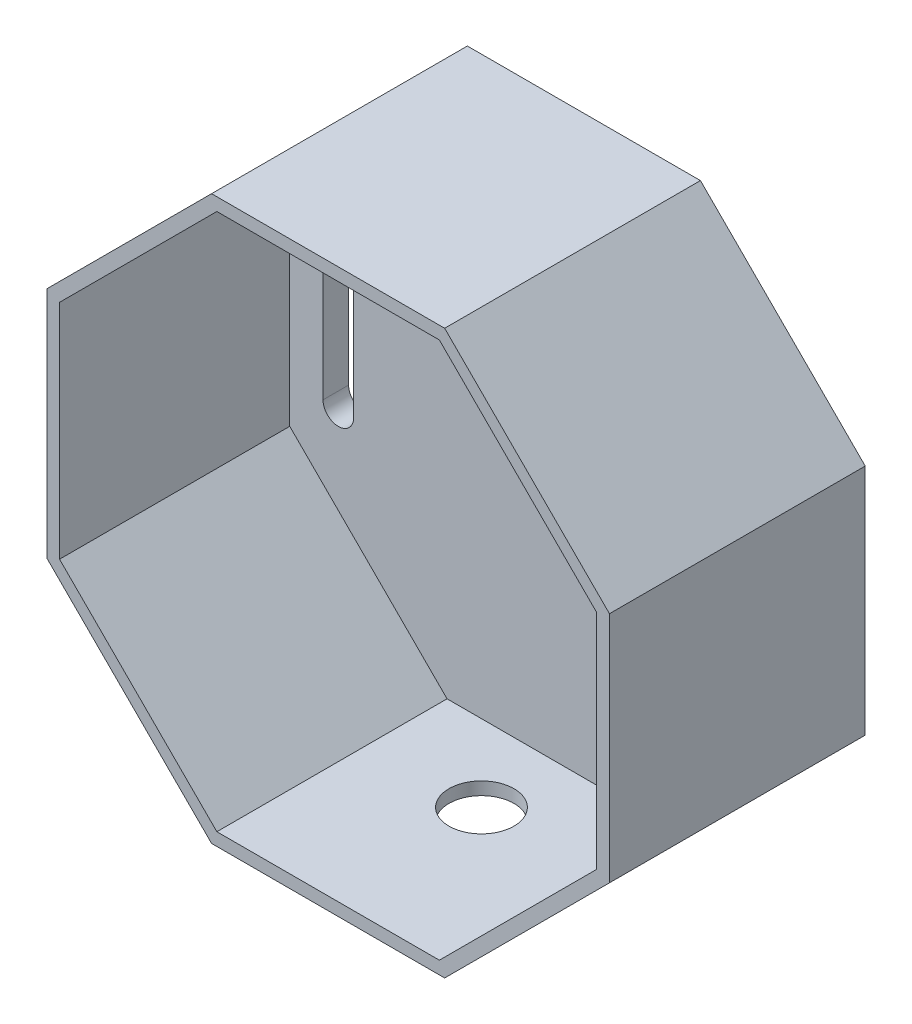
SolidWorks part; units mm, degrees
material "ABS PC"
ref_plane "Front Plane" through (0, 0, 0) normal (0, 0, 1) x (1, 0, 0)
ref_plane "Top Plane" through (0, 0, 0) normal (0, 1, 0) x (1, 0, 0)
ref_plane "Right Plane" through (0, 0, 0) normal (1, 0, 0) x (0, 0, -1)
sketch "Sketch8" plane through (0, 0, 0) normal (0, 0, 1) x (1, 0, 0)
  line L1 (55, 22.7817) -> (22.7817, 55)
  line L2 (22.7817, 55) -> (-22.7817, 55)
  line L3 (-22.7817, 55) -> (-55, 22.7817)
  line L4 (-55, 22.7817) -> (-55, -22.7817)
  line L5 (-55, -22.7817) -> (-22.7817, -55)
  line L6 (-22.7817, -55) -> (22.7817, -55)
  line L7 (22.7817, -55) -> (55, -22.7817)
  line L8 (55, -22.7817) -> (55, 22.7817)
  circle A0 centre (0, 0) radius 55 construction
extrude "Boss-Extrude3" add sketch "Sketch8" along normal blind 50
sketch "Sketch9" plane through (0, 0, 50) normal (0, 0, 1) x (1, 0, 0)
  line L1 (52.5, 21.7462) -> (21.7462, 52.5)
  line L2 (21.7462, 52.5) -> (-21.7462, 52.5)
  line L3 (-21.7462, 52.5) -> (-52.5, 21.7462)
  line L4 (-52.5, 21.7462) -> (-52.5, -21.7462)
  line L5 (-52.5, -21.7462) -> (-21.7462, -52.5)
  line L6 (-21.7462, -52.5) -> (21.7462, -52.5)
  line L7 (21.7462, -52.5) -> (52.5, -21.7462)
  line L8 (52.5, -21.7462) -> (52.5, 21.7462)
  circle A0 centre (0, 0) radius 52.5 construction
extrude "Cut-Extrude3" cut sketch "Sketch9" against normal blind 45
hole_wizard "Hole1" positions "Sketch10" profile "Sketch12" legacy end condition through all
sketch "Sketch10" plane through (0, -52.5, 0) normal (0, 1, 0) x (1, 0, 0)
  point P0 (0, -20.0175)
sketch "Sketch12" plane through (0, -52.5, 20.0175) normal (1, 0, 0) x (0, 0, 1)
  line L0 (0, 0) -> (0, 2.5)
  line L1 (0, 2.5) -> (6.35, 2.5)
  line L2 (6.35, 2.5) -> (6.35, 0)
  line L3 (6.35, 0) -> (0, 0)
  line L4 (0, 110) -> (0, -10) construction
  dimension "Diameter" = 12.7
  dimension "Depth" = 2.5
sketch "Sketch15" plane through (0, 0, 0) normal (0, 0, -1) x (-1, 0, 0)
  line L0 (-43, 13.2597) -> (-43, -13.2907) construction
  line L1 (-40, 13.2597) -> (-40, -13.2907)
  line L2 (-46, 13.2597) -> (-46, -13.2907)
  line L3 (-52.5, -21.7462) -> (-52.5, 21.7462) construction
  arc A0 (-40, 13.2597) -> (-46, 13.2597) centre (-43, 13.2597) ccw
  arc A1 (-46, -13.2907) -> (-40, -13.2907) centre (-43, -13.2907) ccw
  point P2 (-43, -0.0155)
  point P7 (-46, -0.0155)
  point P10 (-40.0412, 13.2597)
  point P11 (0, 0)
  dimension "D1" = 6.5
extrude "Cut-Extrude4" cut sketch "Sketch15" against normal blind 5 and the other way through all
sketch "Sketch18" plane through (0, 0, 0) normal (0, 0, -1) x (-1, 0, 0)
  line L0 (43, 12.9852) -> (43, -14.0148) construction
  line L1 (46, 12.9852) -> (46, -14.0148)
  line L2 (40, 12.9852) -> (40, -14.0148)
  line L3 (52.5, 21.7462) -> (52.5, -21.7462) construction
  arc A0 (46, 12.9852) -> (40, 12.9852) centre (43, 12.9852) ccw
  arc A1 (40, -14.0148) -> (46, -14.0148) centre (43, -14.0148) ccw
  point P2 (43, -0.5148)
  point P7 (42.9105, -14.0148)
  point P10 (46, -0.5148)
  dimension "D1" = 6.5
extrude "Cut-Extrude5" cut sketch "Sketch18" against normal blind 5
